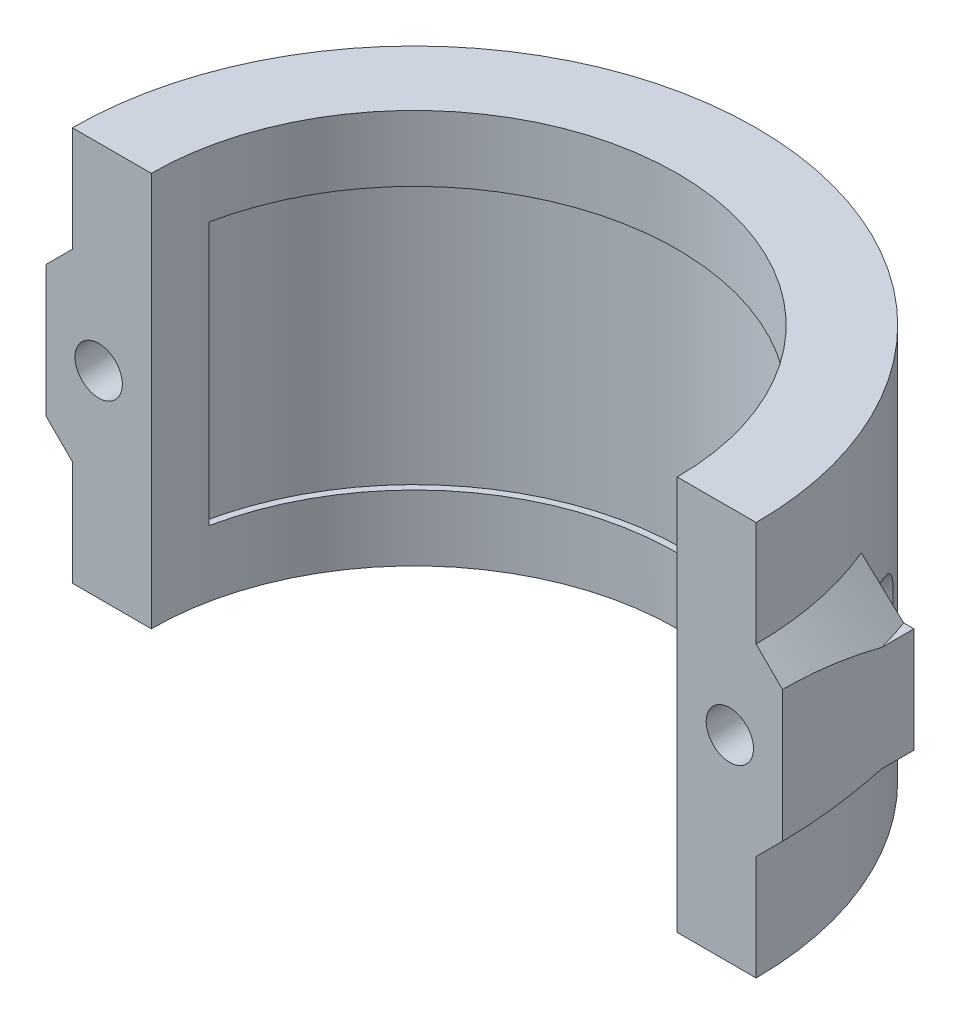
SolidWorks part; units mm, degrees
material "PETG"
ref_plane "Płaszczyzna przednia" through (0, 0, 0) normal (0, 0, 1) x (1, 0, 0)
ref_plane "Płaszczyzna górna" through (0, 0, 0) normal (0, 1, 0) x (1, 0, 0)
ref_plane "Płaszczyzna prawa" through (0, 0, 0) normal (1, 0, 0) x (0, 0, -1)
sketch "Sketch1" plane through (0, 0, 0) normal (0, 1, 0) x (1, 0, 0)
  line L0 (26, 0) -> (20, 0)
  line L1 (-20, 0) -> (-26, 0)
  arc A0 (20, 0) -> (-20, 0) centre (0, 0) ccw
  arc A1 (26, 0) -> (-26, 0) centre (0, 0) ccw
  circle A2 centre (0, 0) radius 26 construction
  circle A3 centre (0, 0) radius 20 construction
  dimension "D1" = 40
  dimension "D2" = 6
extrude "Boss-Extrude1" add sketch "Sketch1" along normal blind 30
sketch "Sketch2" plane through (0, 0, 0) normal (0, 0, 1) x (1, 0, 0)
  line L0 (20, 30) -> (20, 0) construction
  line L1 (20, 19) -> (28, 19)
  line L2 (20, 19) -> (20, 11)
  line L3 (20, 11) -> (28, 11)
  line L4 (28, 19) -> (28, 11)
  line L5 (-20, 30) -> (-20, 0) construction
  line L6 (-20, 11) -> (-28, 11)
  line L7 (-20, 11) -> (-20, 19)
  line L8 (-20, 19) -> (-28, 19)
  line L9 (-28, 11) -> (-28, 19)
  line L10 (0, 0) -> (0, 30) construction
  line L11 (20, 30) -> (-20, 30) construction
  line L12 (0, 15) -> (-28, 15) construction
  dimension "D1" = 8
extrude "Boss-Extrude2" add sketch "Sketch2" against normal blind 10
hole_wizard "Ø4.2 (4.2) Diameter Hole1" [suppressed] positions "Sketch6" profile "Sketch7" hole size "Ø4.2" standard "DIN"
sketch "Sketch6" plane through (0, 0, 0) normal (0, 0, 1) x (1, 0, 0)
  line L0 (0, 0) -> (0, 16.2402) construction
  line L3 (-20, 11) -> (-28, 11)
  line L4 (-20, 11) -> (-20, 19)
  line L5 (-20, 19) -> (-28, 19)
  line L6 (-28, 11) -> (-28, 19)
  line L7 (-20, 11) -> (-28, 19) construction
  line L8 (-20, 19) -> (-28, 11) construction
  line L9 (-26, 19) -> (-28, 19) construction
  line L10 (-28, 11) -> (-26, 11) construction
  line L11 (-28, 19) -> (-28, 11) construction
  point P0 (-24, 15)
  point P9 (24, 15)
  point P10 (-24, 15)
sketch "Sketch7" plane through (-24, 15, 0) normal (1, 0, 0) x (0, -1, 0)
  line L0 (0, 0) -> (0, 26)
  line L1 (0, 26) -> (2.1, 26)
  line L2 (2.1, 26) -> (2.1, 0)
  line L5 (2.1, 0) -> (0, 0)
  line L11 (0, -6.35) -> (0, 107.95) construction
  dimension "Thru Hole Dia." = 4.2
  dimension "Thru Hole Depth" = 26
sketch "Sketch8" plane through (0, 30, 0) normal (0, 1, 0) x (1, 0, 0)
  line L1 (-10, 28) -> (10, 28)
  line L2 (-10, 28) -> (-10, 24)
  line L3 (-10, 24) -> (10, 24)
  line L4 (10, 28) -> (10, 24)
  line L5 (-10, 28) -> (10, 24) construction
  line L6 (-10, 24) -> (10, 28) construction
  arc A0 (26, 0) -> (-26, 0) centre (0, 0) ccw construction
  point P0 (0, 26)
  dimension "D1" = 20
extrude "Boss-Extrude3" [suppressed] add sketch "Sketch8" against normal up to surface (30 mm away)
hole_wizard "CBORE for M3 Hex Socket Head Cap Screw4" positions "Sketch19" profile "Sketch20" counterbore size "M3" standard "DIN" end condition through all
sketch "Sketch19" plane through (0, 0, -10) normal (0, 0, -1) x (-1, 0, 0)
  line L1 (-28, 11) -> (-20, 11)
  line L2 (-28, 11) -> (-28, 19)
  line L3 (-28, 19) -> (-20, 19)
  line L4 (-20, 11) -> (-20, 19)
  line L5 (-28, 11) -> (-20, 19) construction
  line L6 (-28, 19) -> (-20, 11) construction
  line L7 (-28, 11) -> (-28, 19) construction
  line L8 (-24, 11) -> (-28, 11) construction
  line L9 (-28, 19) -> (-24, 19) construction
  line L10 (0, 0) -> (0, 32.9408)
  point P5 (-24, 15)
  point P63 (24, 15)
sketch "Sketch20" plane through (24, 15, -10) normal (1, 0, 0) x (0, 1, 0)
  line L0 (0, 0) -> (0, 10)
  line L1 (0, 10) -> (1.8, 10)
  line L3 (1.8, 10) -> (1.8, 3.4)
  line L4 (1.8, 3.4) -> (3.25, 3.4)
  line L5 (3.25, 3.4) -> (3.25, 0)
  line L7 (3.25, 0) -> (0, 0)
  line L11 (0, -6.35) -> (0, 107.95) construction
  dimension "Thru Hole Dia." = 3.6
  dimension "Thru Hole Depth" = 10
  dimension "C'Bore Dia." = 6.5
  dimension "C'Bore Depth" = 3.4
sketch "Sketch21" plane through (0, 0, -6.6) normal (0, 0, -1) x (-1, 0, 0)
  circle A0 centre (24, 15) radius 3.25 construction
  circle A1 centre (-24, 15) radius 3.25 construction
  circle A2 centre (24, 15) radius 3.25
  circle A3 centre (-24, 15) radius 3.25
extrude "Cut-Extrude2" cut sketch "Sketch21" along normal through all
sketch "Sketch22" plane through (0, 30, 0) normal (0, 1, 0) x (1, 0, 0)
  line L5 (-20.106, 4) -> (-19.5959, 4)
  line L6 (19.5959, 4) -> (20.106, 4)
  arc A2 (19.5959, 4) -> (-19.5959, 4) centre (0, 0) ccw
  arc A3 (20.106, 4) -> (-20.106, 4) centre (0, 0) ccw
  circle A4 centre (0, 0) radius 20.5 construction
  circle A5 centre (0, 0) radius 20 construction
  dimension "D1" = 4
  dimension "D2" = 0.5
extrude "Cut-Extrude3" cut sketch "Sketch22" against normal blind 20 from offset 5 offset against normal yes
hole_wizard "Ø4.2 (4.2) Diameter Hole2" [suppressed] positions "Sketch23" profile "Sketch24" hole size "Ø4.2" standard "DIN"
sketch "Sketch23" plane through (0, 0, -28) normal (0, 0, -1) x (-1, 0, 0)
  point P0 (0, 20)
  point P2 (0, 10)
  dimension "D1" = 10
  dimension "D2" = 10
sketch "Sketch24" plane through (0, 20, -28) normal (1, 0, 0) x (0, 1, 0)
  line L0 (0, 0) -> (0, 28)
  line L1 (0, 28) -> (2.1, 28)
  line L2 (2.1, 28) -> (2.1, 0)
  line L5 (2.1, 0) -> (0, 0)
  line L11 (0, -6.35) -> (0, 107.95) construction
  dimension "Thru Hole Dia." = 4.2
  dimension "Thru Hole Depth" = 28
chamfer "Chamfer1" distance 3 angle 45 4 edges at (25.4951, 11, -5.099) (25.4951, 19, -5.099) (-25.4951, 19, -5.099) (-25.4951, 11, -5.099)
